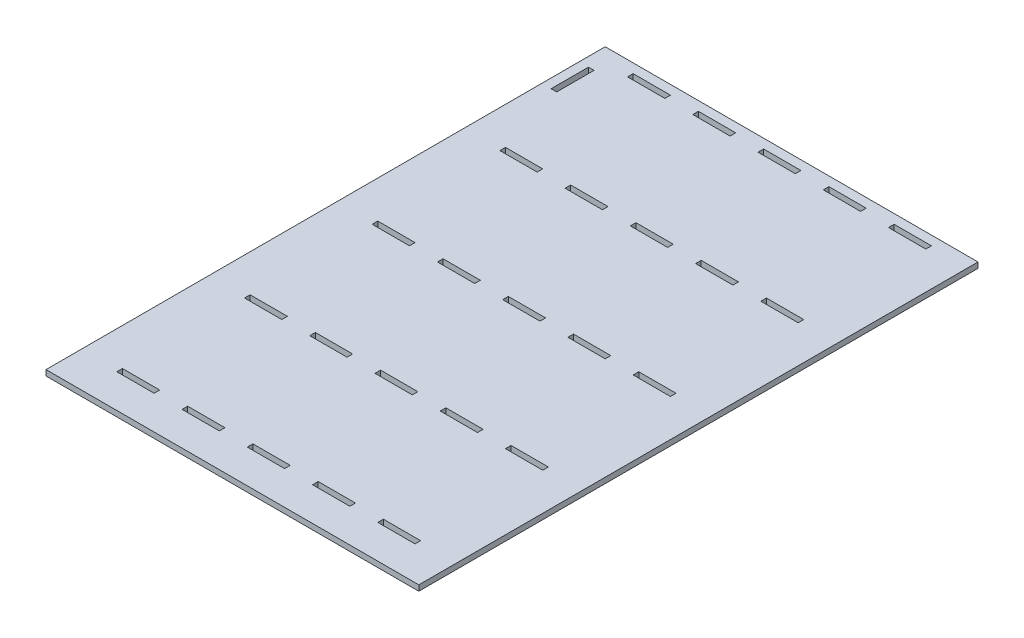
SolidWorks part; units mm, degrees
ref_plane "Front Plane" through (0, 0, 0) normal (0, 0, 1) x (1, 0, 0)
ref_plane "Top Plane" through (0, 0, 0) normal (0, 1, 0) x (1, 0, 0)
ref_plane "Right Plane" through (0, 0, 0) normal (1, 0, 0) x (0, 0, -1)
sketch "Sketch1" plane through (0, 0, 0) normal (0, 1, 0) x (1, 0, 0)
  line L1 (0, 0) -> (200, 0)
  line L2 (0, 0) -> (0, 300)
  line L3 (0, 300) -> (200, 300)
  line L4 (200, 0) -> (200, 300)
  line L5 (0, 0) -> (200, 300) construction
  line L6 (0, 300) -> (200, 0) construction
  line L7 (20, 295) -> (40, 295)
  line L8 (20, 295) -> (20, 292)
  line L9 (20, 292) -> (40, 292)
  line L10 (40, 295) -> (40, 292)
  line L11 (20, 295) -> (40, 292) construction
  line L12 (20, 292) -> (40, 295) construction
  line L13 (5, 286) -> (8, 286)
  line L14 (5, 286) -> (5, 266)
  line L15 (5, 266) -> (8, 266)
  line L16 (8, 286) -> (8, 266)
  line L17 (5, 286) -> (8, 266) construction
  line L18 (5, 266) -> (8, 286) construction
  line L38 (0, 150) -> (200, 150) construction
  line L39 (100, 300) -> (100, 0) construction
  point P4 (0, 0)
  point P10 (30, 293.5)
  point P15 (6.5, 276)
  dimension "D1" = 300
  dimension "D2" = 200
  dimension "D3" = 3
  dimension "D4" = 20
  dimension "D5" = 5
  dimension "D6" = 5
  dimension "D7" = 14
  dimension "D8" = 20
extrude "Boss-Extrude1" add sketch "Sketch1" along normal blind 3 contours L1 L4 L3 L2 L7 L10 L9 L8 L13 L16 L15 L14 | L10 L7 L8 L9 | L16 L13 L14 L15 region at (100.1638, 0, -149.73) region at (30, 0, -293.5) region at (6.5, 0, -276)
sketch "Sketch2" plane through (0, 3, 0) normal (0, 1, 0) x (1, 0, 0)
  line L0 (5, 266) -> (8, 266) construction
  line L1 (8, 286) -> (8, 266) construction
  line L2 (5, 286) -> (5, 266) construction
  line L3 (5, 286) -> (8, 286) construction
  line L4 (8, 286) -> (5, 286)
  line L5 (8, 266) -> (8, 286)
  line L6 (5, 266) -> (8, 266)
  line L7 (5, 286) -> (5, 266)
  line L8 (8, 286) -> (5, 286)
  line L9 (8, 266) -> (8, 286)
  line L10 (5, 266) -> (8, 266)
  line L11 (5, 286) -> (5, 266)
  line L12 (40, 295) -> (20, 295)
  line L13 (40, 292) -> (40, 295)
  line L14 (20, 292) -> (40, 292)
  line L15 (20, 295) -> (20, 292)
  line L16 (40, 295) -> (20, 295)
  line L17 (40, 292) -> (40, 295)
  line L18 (20, 292) -> (40, 292)
  line L19 (20, 295) -> (20, 292)
  line L20 (0, 0) -> (200, 0)
  line L21 (200, 0) -> (200, 300)
  line L22 (200, 300) -> (0, 300)
  line L23 (0, 300) -> (0, 0)
  line L24 (0, 0) -> (200, 0)
  line L25 (200, 0) -> (200, 300)
  line L26 (200, 300) -> (0, 300)
  line L27 (0, 300) -> (0, 0)
  line L28 (20, 295) -> (20, 292) construction
  line L29 (40, 295) -> (40, 292) construction
  line L30 (20, 292) -> (40, 292) construction
  line L31 (20, 295) -> (40, 295) construction
  line L32 (5, 266) -> (8, 266)
  line L33 (8, 286) -> (8, 266)
  line L34 (5, 286) -> (5, 266)
  line L35 (5, 286) -> (8, 286)
  line L36 (20, 295) -> (20, 292)
  line L37 (40, 295) -> (40, 292)
  line L38 (20, 292) -> (40, 292)
  line L39 (20, 295) -> (40, 295)
  dimension "D1" = 0
  dimension "D2" = 0
  dimension "D3" = 0
extrude "Cut-Extrude2" cut sketch "Sketch2" against normal blind 10 contours L16 L19 L18 L17 | L8 L11 L10 L9 region at (6.5, 3, -276) region at (30, 3, -293.5)
pattern_linear "LPattern3" count 5 spacing 35 along (1, 0, 0) count 5 spacing 68.5 along (0, 0, 1) of face at (30, 1.5, -292) of face at (20, 1.5, -293.5) of face at (30, 1.5, -295) of face at (40, 1.5, -293.5)
pattern_linear "LPattern4" count 3 spacing 93.5 count 8 spacing 35 rebuild error yes
sketch "Sketch4" plane through (0, 3, 0) normal (0, 1, 0) x (1, 0, 0)
  line L1 (6.5, 293.5) -> (100, 293.5)
  line L2 (6.5, 293.5) -> (6.5, 223.5)
  line L3 (6.5, 223.5) -> (100, 223.5)
  line L4 (100, 293.5) -> (100, 223.5)
  line L5 (20, 21) -> (20, 18) construction
  line L6 (5, 231) -> (8, 231) construction
  line L7 (100, 300) -> (100, 0) construction
  line L9 (6.5, 223.5) -> (100, 223.5)
  line L10 (6.5, 223.5) -> (6.5, 153.5)
  line L11 (6.5, 153.5) -> (100, 153.5)
  line L12 (100, 223.5) -> (100, 153.5)
  line L15 (6.5, 153.5) -> (100, 153.5)
  line L16 (6.5, 153.5) -> (6.5, 83.5)
  line L17 (6.5, 83.5) -> (100, 83.5)
  line L18 (100, 153.5) -> (100, 83.5)
  line L21 (6.5, 83.5) -> (100, 83.5)
  line L22 (6.5, 83.5) -> (6.5, 19.5)
  line L23 (6.5, 19.5) -> (100, 19.5)
  line L24 (100, 83.5) -> (100, 19.5)
  point P5 (0, 0)
  point P6 (0, 0)
  point P11 (0, 0)
  point P14 (0, 0)
  point P18 (20, 19.5)
  dimension "D1" = 7.5
